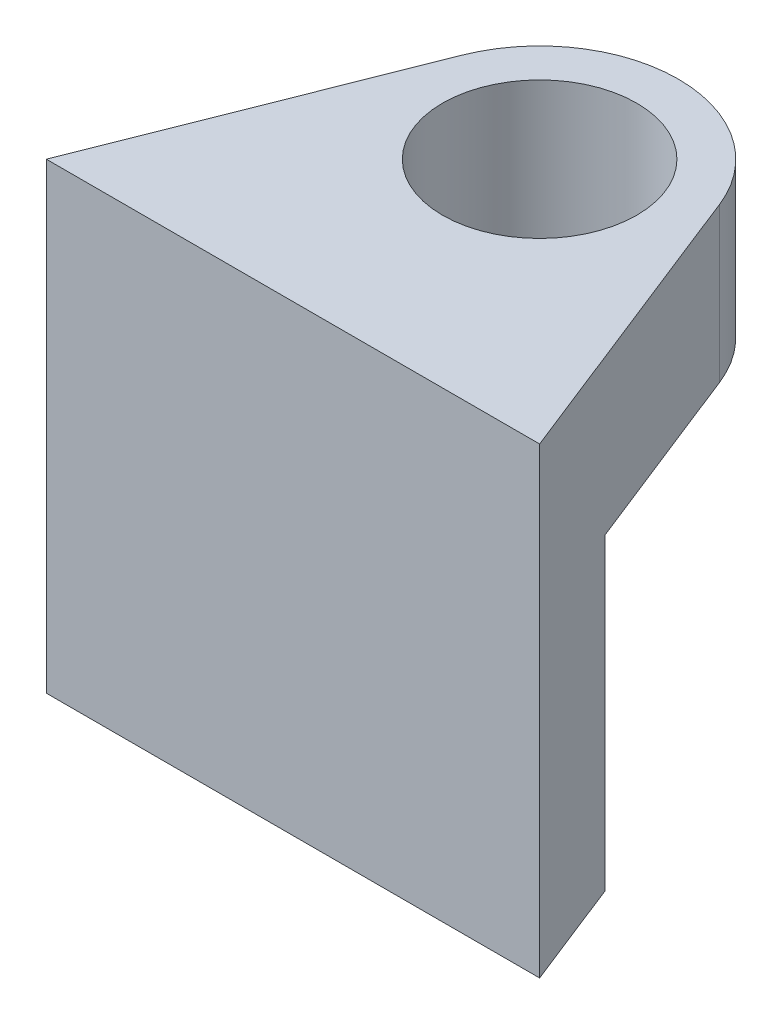
SolidWorks part; units mm, degrees
ref_plane "Front Plane" through (0, 0, 0) normal (0, 0, 1) x (1, 0, 0)
ref_plane "Top Plane" through (0, 0, 0) normal (0, 1, 0) x (1, 0, 0)
ref_plane "Right Plane" through (0, 0, 0) normal (1, 0, 0) x (0, 0, -1)
sketch "Sketch2" plane through (0, 0, 0) normal (0, 1, 0) x (1, 0, 0)
  line L0 (-8, -8) -> (8, -8)
  line L1 (8, -8) -> (4.1851, 1.6538)
  line L2 (-8, -8) -> (-4.1851, 1.6538)
  arc A0 (4.1851, 1.6538) -> (-4.1851, 1.6538) centre (0, 0) ccw
  circle A1 centre (0, 0) radius 3.15
  dimension "D1" = 9
  dimension "D2" = 6.3
  dimension "D3" = 8
  dimension "D4" = 8
  dimension "D5" = 8
extrude "Boss-Extrude1" add sketch "Sketch2" along normal blind 5
sketch "Sketch3" plane through (0, 0, 0) normal (0, -1, 0) x (1, 0, 0)
  line L0 (8, 8) -> (6.6169, 4.5)
  line L1 (8, 8) -> (4.1851, -1.6538) construction
  line L2 (6.6169, 4.5) -> (-6.6169, 4.5)
  line L3 (-4.1851, -1.6538) -> (-8, 8) construction
  line L4 (-6.6169, 4.5) -> (-8, 8)
  line L5 (-8, 8) -> (8, 8)
  dimension "D1" = 3.5
extrude "Boss-Extrude3" add sketch "Sketch3" along normal blind 10
